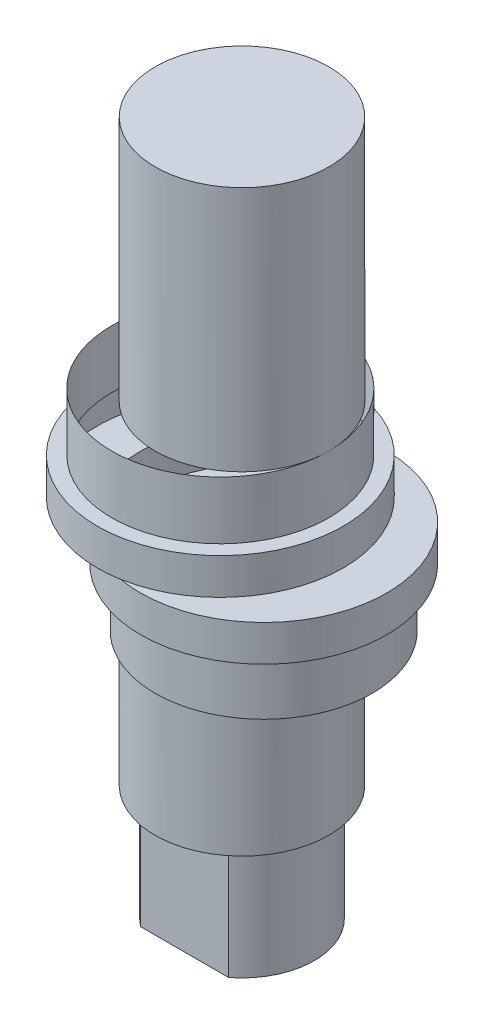
SolidWorks part; units mm, degrees
ref_plane "Front Plane" through (0, 0, 0) normal (0, 0, 1) x (1, 0, 0)
ref_plane "Top Plane" through (0, 0, 0) normal (0, 1, 0) x (1, 0, 0)
ref_plane "Right Plane" through (0, 0, 0) normal (1, 0, 0) x (0, 0, -1)
sketch "Sketch1" plane through (0, 0, 0) normal (0, 0, 1) x (1, 0, 0)
  line L0 (0, 0) -> (0, 40)
  line L1 (-1.5, 0) -> (-1.5, 40) construction
  line L2 (-1.5, 40) -> (1.5, 40) construction
  line L3 (-1.5, 0) -> (1.5, 0) construction
  line L4 (1.5, 0) -> (1.5, 40) construction
  line L6 (-6, 14) -> (9, 14)
  line L7 (-6, 14) -> (-6, 10)
  line L8 (-6, 10) -> (9, 10)
  line L9 (9, 14) -> (9, 10)
  line L10 (-6, 14) -> (9, 10) construction
  line L11 (-6, 10) -> (9, 14) construction
  line L12 (-9, 23) -> (6, 23)
  line L13 (-9, 23) -> (-9, 19)
  line L14 (-9, 19) -> (6, 19)
  line L15 (6, 23) -> (6, 19)
  line L16 (-9, 23) -> (6, 19) construction
  line L17 (-9, 19) -> (6, 23) construction
  line L20 (-6, 0) -> (6, 0)
  line L21 (-6, 0) -> (-6, 40)
  line L22 (-6, 40) -> (6, 40)
  line L23 (6, 0) -> (6, 40)
  line L24 (-6, 0) -> (6, 40) construction
  line L25 (-6, 40) -> (6, 0) construction
  point P7 (1.5, 12)
  point P12 (-1.5, 21)
  point P19 (0, 20)
  point P24 (0, 20)
  dimension "D1" = 3
  dimension "D2" = 40
  dimension "D3" = 15
  dimension "D4" = 4
  dimension "D5" = 5
  dimension "D6" = 12
revolve "Revolve4" add sketch "Sketch1" angle 360 about L0 region at (-3, 5, 0) region at (-3, 12, 0) region at (-3, 16.5, 0) region at (-3, 21, 0) region at (-3, 31.5, 0)
revolve "Revolve5" add sketch "Sketch1<5>" angle 360 about L1 region at (-7.5, 21, 0)
sketch "Sketch1<5>" plane through (0, 0, 0) normal (0, 0, 1) x (1, 0, 0) same geometry as "Sketch1"
revolve "Revolve6" add sketch "Sketch1<6>" angle 360 about L4 region at (7.5, 12, 0)
sketch "Sketch1<6>" plane through (0, 0, 0) normal (0, 0, 1) x (1, 0, 0) same geometry as "Sketch1"
sketch "Sketch2" plane through (0, 0, 0) normal (0, 0, 1) x (1, 0, 0)
  line L2 (0, 19) -> (0, 14) construction
  line L7 (-6, 19) -> (6, 19) construction
  line L10 (9, 14) -> (-6, 14) construction
  line L16 (-1.5, 19) -> (-1.5, 14) construction
  line L17 (1.5, 19) -> (1.5, 14) construction
  line L26 (-9, 19) -> (6, 19) construction
  line L27 (9, 14) -> (-6, 14) construction
  line L28 (-9, 19) -> (6, 19) construction
  line L29 (9, 10) -> (9, 14) construction
  line L30 (-1.5, 19) -> (-10, 19)
  line L31 (-1.5, 19) -> (-1.5, 16.5)
  line L32 (-1.5, 16.5) -> (-10, 16.5)
  line L33 (-10, 19) -> (-10, 16.5)
  line L34 (1.5, 16.5) -> (10, 16.5)
  line L35 (1.5, 16.5) -> (1.5, 14)
  line L36 (1.5, 14) -> (10, 14)
  line L37 (10, 16.5) -> (10, 14)
  dimension "D1" = 1
revolve "Revolve7" add sketch "Sketch2" angle 360 about L16 region at (-5.75, 17.75, 0)
revolve "Revolve8" add sketch "Sketch2<3>" angle 360 about L17 region at (5.75, 15.25, 0)
sketch "Sketch2<3>" plane through (0, 0, 0) normal (0, 0, 1) x (1, 0, 0) same geometry as "Sketch2"
sketch "Sketch3" plane through (0, 0, 0) normal (0, -1, 0) x (1, 0, 0)
  line L0 (-3.0412, 3.9688) -> (3.0412, 3.9688)
  line L1 (-3.0412, -3.9688) -> (3.0412, -3.9688)
  line L2 (0, -3.9688) -> (0, 0) construction
  line L3 (0, 0) -> (0, 3.9688) construction
  circle A0 centre (0, 0) radius 5
  dimension "D1" = 10
  dimension "D2" = 7.9375
extrude "Boss-Extrude1" add sketch "Sketch3" along normal blind 8 contours L1 A0 L0 region at (0, 0, 0)
sketch "Sketch4" plane through (0, -8, 0) normal (0, -1, 0) x (1, 0, 0)
  circle A0 centre (0, 0) radius 1.55
  dimension "D1" = 3.1
extrude "Cut-Extrude1" cut sketch "Sketch4" against normal up to surface (8 mm away) up to face at (0, 0, 0)
equation "\"Ratio\"= 15"
equation "\"Hull Diameter\"= 3.5in"
equation "\"Fixed Ring Diameter\"= 76"
equation "\"Fixed Pin Diameter\"= 6"
equation "\"Output Ring Diameter\"= 40"
equation "\"Output Pin Diameter\"= 6"
equation "\"Disk Bearing Inner Diameter\"= 9"
equation "\"Disk Bearing Outer Diameter\"= 17"
equation "\"Disk Bearing Height\"= 5"
equation "\"Shaft Bearing Inner Diameter\"= 15"
equation "\"Shaft Bearing Outer Diameter\"= 21"
equation "\"Shaft Bearing Height\"= 4"
equation "\"Eccentricity\"= 1.5"
equation "\"Disk Height\"= 8"
equation "\"Disk Spacing\"= 5"
equation "\"Hull Height\"= 40"
equation "\"Shaft End Bearing Inner Diameter\"= 12"
equation "\"Shaft End Bearing Outer Diameter\"= 18"
equation "\"Shaft End Bearing Height\"= 4"
equation "\"Output Bearing Inner Diameter\"= 55"
equation "\"Output Bearing Outer Diameter\"= 72"
equation "\"Outer Bearing Height\"= 9"
equation "\"D1@Sketch1\"=\"Eccentricity\"*2"
equation "\"D2@Sketch1\"=\"Hull Height\""
equation "\"D3@Sketch1\"=\"Shaft Bearing Inner Diameter\""
equation "\"D4@Sketch1\"=\"Shaft Bearing Height\""
equation "\"D5@Sketch1\"=\"Disk Spacing\""
